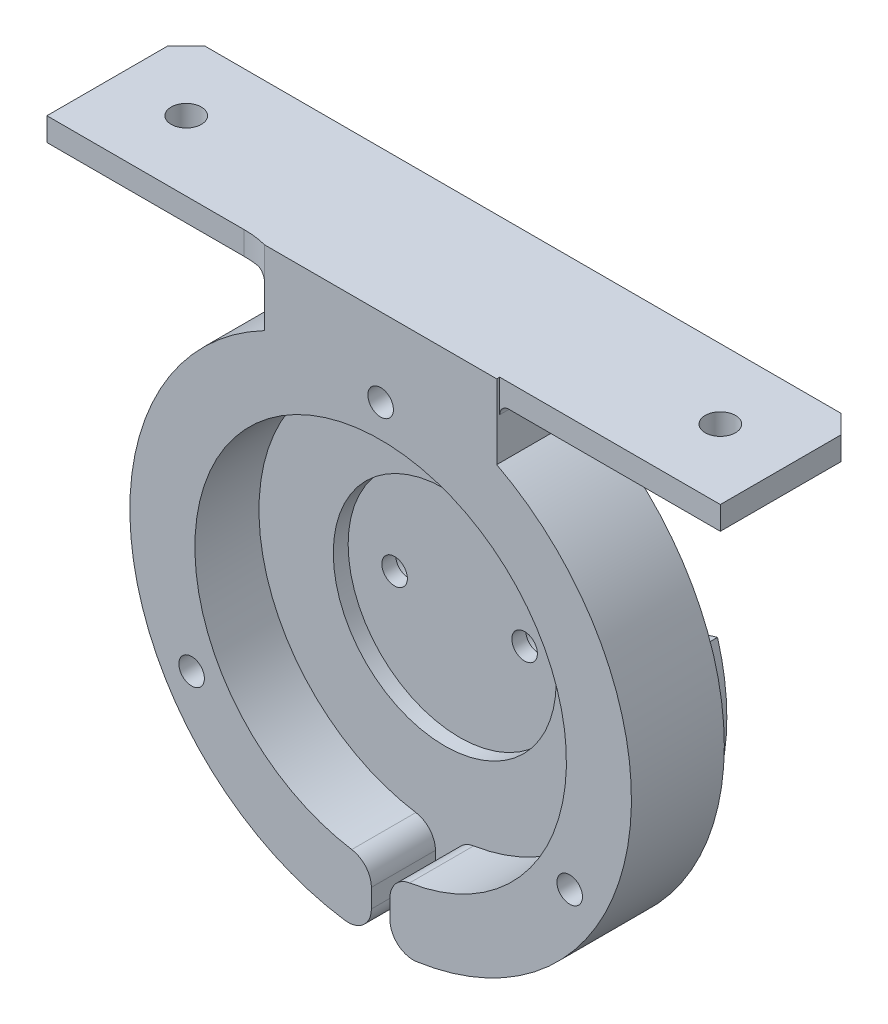
SolidWorks part; units mm, degrees
ref_plane "Front Plane" through (0, 0, 0) normal (0, 0, 1) x (1, 0, 0)
ref_plane "Top Plane" through (0, 0, 0) normal (0, 1, 0) x (1, 0, 0)
ref_plane "Right Plane" through (0, 0, 0) normal (1, 0, 0) x (0, 0, -1)
sketch "Sketch1" plane through (0, 0, 0) normal (0, 0, 1) x (1, 0, 0)
  circle A0 centre (0, 0) radius 27
  circle A1 centre (0, 0) radius 23.5 construction
  circle A2 centre (0, 23.5) radius 1.375
  circle A3 centre (20.3516, -11.75) radius 1.375
  circle A4 centre (-20.3516, -11.75) radius 1.375
  circle A6 centre (0, 0) radius 20
  point P15 (0, 0)
  dimension "D1" = 54
  dimension "D2" = 47
  dimension "D3" = 2.75
  dimension "D5" = 40
  dimension "D4" = 3
extrude "Boss-Extrude1" add sketch "Sketch1" along normal blind 10
sketch "Sketch3" plane through (0, 0, 0) normal (0, 0, 1) x (1, 0, 0)
  circle A0 centre (0, 0) radius 20
  circle A1 centre (0, 0) radius 7 construction
  circle A2 centre (-7, 0) radius 1.375
  circle A3 centre (7, 0) radius 1.375
  circle A4 centre (0, 0) radius 11.5 construction
  dimension "D1" = 40
  dimension "D2" = 14
  dimension "D3" = 2.75
  dimension "D4" = 23
extrude "Boss-Extrude2" add sketch "Sketch3" along normal blind 1.5
sketch "Sketch5" plane through (0, 0, 10) normal (0, 0, 1) x (1, 0, 0)
  line L0 (0, -55) -> (0, 55) construction
  line L1 (-12.5, 23.9322) -> (-4.2519, 23.9322)
  line L2 (-12.5, 23.9322) -> (-12.5, 31.9322)
  line L3 (-12.5, 31.9322) -> (12.5, 31.9322)
  line L4 (12.5, 23.9322) -> (12.5, 31.9322)
  line L5 (4.2678, 23.9322) -> (0, 26.2545)
  line L6 (0, 26.2545) -> (-4.2519, 23.9322)
  line L7 (4.2678, 23.9322) -> (12.5, 23.9322)
  circle A0 centre (0, 0) radius 27 construction
  dimension "D1" = 12.5
  dimension "D2" = 25
  dimension "D3" = 8
extrude "Boss-Extrude3" add sketch "Sketch5" against normal blind 6
sketch "Sketch6" plane through (0, 31.9322, 0) normal (0, 1, 0) x (1, 0, 0)
  line L0 (12.5, -4) -> (12.5, -10) construction
  line L1 (-12.5, -10) -> (12.5, -10)
  line L2 (-12.5, -10) -> (-12.5, 5.32)
  line L3 (-12.5, 5.32) -> (12.5, 5.32)
  line L4 (12.5, -10) -> (12.5, 5.32)
  dimension "D1" = 15.32
extrude "Boss-Extrude4" add sketch "Sketch6" against normal blind 2.5
sketch "Sketch7" plane through (0, 31.9322, 0) normal (0, 1, 0) x (1, 0, 0)
  line L0 (0, -55) -> (0, 55) construction
  line L1 (-36.25, -67.18) -> (36.25, -67.18) construction
  line L2 (-36.25, -67.18) -> (-36.25, 1.32) construction
  line L3 (-32.25, 5.32) -> (32.25, 5.32) construction
  line L4 (36.25, -67.18) -> (36.25, 1.32) construction
  line L5 (-28.75, -9.68) -> (-36.25, -9.68)
  line L6 (0, 5.32) -> (-36.25, 5.32)
  line L7 (-36.25, -9.68) -> (-36.25, -2.18)
  line L8 (12.5, -4) -> (-12.5, -4) construction
  line L9 (0, 5.32) -> (0, -9.68)
  line L10 (0, -9.68) -> (-28.75, -9.68)
  line L11 (-36.25, 5.32) -> (-36.25, -2.18)
  arc A0 (32.25, 5.32) -> (36.25, 1.32) centre (32.25, 1.32) cw construction
  circle A3 centre (-28.75, -2.18) radius 1.625
  point P4 (0, 5.32)
  point P11 (36.25, 5.32)
  point P14 (-36.25, 5.32)
  point P21 (-36.25, -9.68)
  dimension "D4" = 4
  dimension "D7" = 3.25
  dimension "D1" = 72.5
  dimension "D2" = 72.5
  dimension "D3" = 9.32
  dimension "D5" = 15
extrude "Boss-Extrude5" add sketch "Sketch7" against normal blind 2.5 contours L10 L9 L6 L11 A3 region at (-17.9604, 31.9322, 2.18)
fillet "Fillet2" radius 10 1 edges at (-12.5, 30.6822, 9.68)
sketch "Sketch8" plane through (0, 31.9322, 0) normal (0, 1, 0) x (1, 0, 0)
  circle A0 centre (-28.75, -2.18) radius 2.5
  circle A1 centre (-28.75, -2.18) radius 4
  dimension "D1" = 5
  dimension "D2" = 8
extrude "Boss-Extrude6" [suppressed] add sketch "Sketch8" against normal blind 5
mirror "Mirror1" about plane through (0, 0, 0) normal (1, 0, 0) of "Boss-Extrude4", "Boss-Extrude5", "Boss-Extrude6"
fillet "Fillet3" radius 1 3 edges at (0, 29.4322, 4) (12.5, 29.4322, 6.84) (-12.5, 29.4322, 7)
fillet "Fillet4" [suppressed] radius 10
chamfer "Chamfer1" distance 2 angle 45 2 edges at (-36.25, 30.6822, -5.32) (36.25, 30.6822, -5.32)
sketch "Sketch14" plane through (0, 0, 1.5) normal (0, 0, 1) x (1, 0, 0)
  circle A0 centre (0, 0) radius 12
  circle A1 centre (0, 0) radius 20
  dimension "D1" = 24
extrude "Boss-Extrude10" add sketch "Sketch14" along normal blind 1.6
sketch "Sketch9" plane through (0, 0, 1.5) normal (0, 0, 1) x (1, 0, 0)
  circle A0 centre (0, 0) radius 12
  circle A1 centre (0, 0) radius 20
  dimension "D1" = 24
extrude "Boss-Extrude7" [suppressed] add sketch "Sketch9" along normal up to surface (8.5 mm away)
sketch "Sketch4" plane through (0, 0, 0) normal (0, 1, 0) x (1, 0, 0)
  line L0 (12.5, -10) -> (-12.5, -10) construction
  line L1 (-1, -3.1) -> (1, -3.1)
  line L2 (-1, -3.1) -> (-1, -10)
  line L3 (-1, -10) -> (1, -10)
  line L4 (1, -3.1) -> (1, -10)
  line L6 (-12, -3.1) -> (12, -3.1) construction
  point P7 (0, -3.1)
  dimension "D2" = 2
extrude "Cut-Extrude1" cut sketch "Sketch4" against normal up to surface (26.9815 mm away) up to face at (0, 11.9661, 7)
fillet "Fillet6" [suppressed] radius 2
sketch "Sketch10" [suppressed] plane through (0, 0, 10) normal (0, 0, 1) x (1, 0, 0)
  line L0 (-4.25, -19.5432) -> (-4.25, -13.8632)
  line L1 (-1.75, -24.7171) -> (-1.75, -13.4884) construction
  line L2 (0, -8.4586) -> (0, 8.4586) construction
  line L3 (4.25, -19.5432) -> (4.25, -13.8632)
  arc A0 (4.25, -19.5432) -> (-4.25, -19.5432) centre (0, 0) ccw
  arc A1 (-12.5, 23.9322) -> (-4.05, -26.6945) centre (0, 0) ccw construction
  arc A2 (4.25, -13.8632) -> (-4.25, -13.8632) centre (0, 0) ccw
  circle A3 centre (0, 0) radius 12 construction
  dimension "D1" = 7
  dimension "D2" = 2.5
  dimension "D3" = 2.5
extrude "Cut-Extrude2" [suppressed] cut sketch "Sketch10" against normal up to surface (6.5 mm away)
sketch "Sketch12" plane through (0, 0, 0) normal (0, 0, -1) x (-1, 0, 0)
  line L2 (0, 55) -> (0, -55) construction
  line L3 (-3.75, 5.6125) -> (-2.6485, 4.2998)
  line L4 (55, 0) -> (-55, 0) construction
  line L5 (3.75, 5.6125) -> (2.6485, 4.2998)
  arc A0 (2.6485, 4.2998) -> (-2.6485, 4.2998) centre (0, 0) ccw construction
  arc A1 (-2.6485, 4.2998) -> (2.6485, 4.2998) centre (0, 0) cw
  circle A2 centre (0, 0) radius 6.75 construction
  arc A3 (3.75, 5.6125) -> (-3.75, 5.6125) centre (0, 0) ccw
  circle A4 centre (0, 0) radius 5.05 construction
  dimension "D1" = 10.1
  dimension "D2" = 13.5
  dimension "D3" = 3.75
  dimension "D4" = 3.75
  dimension "D5" = 50
  dimension "D6" = 50
extrude "Boss-Extrude8" [suppressed] add sketch "Sketch12" along normal blind 4.5
fillet "Fillet7" [suppressed] radius 1
sketch "Sketch13" plane through (0, 0, 0) normal (0, 0, -1) x (-1, 0, 0)
  circle A0 centre (0, 0) radius 2.5
  dimension "D1" = 5
extrude "Boss-Extrude9" add sketch "Sketch13" along normal blind 5.27
fillet "Fillet9" radius 2.5 4 edges at (1, -26.9815, 6.55) (-1, -26.9815, 6.55) (-1, -19.975, 6.55) (1, -19.975, 6.55)
sketch "Sketch15" plane through (0, 0, 0) normal (0, 0, -1) x (-1, 0, 0)
  circle A0 centre (0, 0) radius 12.5
  dimension "D1" = 25
extrude "Boss-Extrude11" add sketch "Sketch15" along normal blind 2.77
sketch "Sketch16" plane through (0, 0, -2.77) normal (0, 0, -1) x (-1, 0, 0)
  circle A0 centre (7, 0) radius 2.5
  circle A1 centre (-7, 0) radius 2.5
  dimension "D1" = 5
extrude "Cut-Extrude3" cut sketch "Sketch16" against normal up to surface (2.77 mm away) up to face at (12.5, 0, 0)
fillet "Fillet10" radius 1.75 1 edges at (-2.5, 0, -5.27)
sketch "Sketch17" plane through (0, 0, 0) normal (0, 0, -1) x (-1, 0, 0)
  line L1 (0, 8.4586) -> (0, -8.4586) construction
  line L3 (0, 0) -> (26.3369, -25.0236) construction
  line L4 (0, 0) -> (36.8094, -10.8788) construction
  line L5 (8.4586, 0) -> (-8.4586, 0) construction
  line L6 (0, 0) -> (36.8094, 10.8788) construction
  line L7 (23.4954, 6.9439) -> (21.5774, 6.3771)
  line L8 (23.4954, -6.9439) -> (21.5774, -6.3771)
  line L9 (16.3114, -15.498) -> (17.7613, -16.8756)
  line L10 (0, 0) -> (-26.3369, -25.0236) construction
  line L11 (0, 0) -> (-36.8094, -10.8788) construction
  line L12 (-21.5774, -6.3771) -> (-23.4954, -6.9439)
  line L13 (-16.3114, -15.498) -> (-17.7613, -16.8756)
  line L14 (-23.4954, 6.9439) -> (-21.5774, 6.3771)
  arc A0 (22.9619, -5) -> (-22.9619, -5) centre (0, 0) cw construction
  arc A3 (23.4954, -6.9439) -> (23.4954, 6.9439) centre (0, 0) ccw
  arc A4 (21.5774, -6.3771) -> (21.5774, 6.3771) centre (0, 0) ccw
  arc A5 (-16.3114, -15.498) -> (16.3114, -15.498) centre (0, 0) ccw
  arc A6 (-21.5774, 6.3771) -> (-21.5774, -6.3771) centre (0, 0) ccw
  arc A7 (-23.4954, 6.9439) -> (-23.4954, -6.9439) centre (0, 0) ccw
  circle A8 centre (20.3516, -11.75) radius 1.375 construction
  arc A9 (-17.7613, -16.8756) -> (17.7613, -16.8756) centre (0, 0) ccw
  circle A10 centre (0, 0) radius 22.5 construction
  circle A11 centre (0, 0) radius 24.5 construction
  point P28 (-16.3113, -15.4981)
  dimension "D4" = 5.5
  dimension "D1" = 45
  dimension "D2" = 49
  dimension "D5" = 5.5
extrude "Boss-Extrude12" add sketch "Sketch17" along normal up to surface (2.77 mm away) up to face at (-9.5, 0, -2.77)
